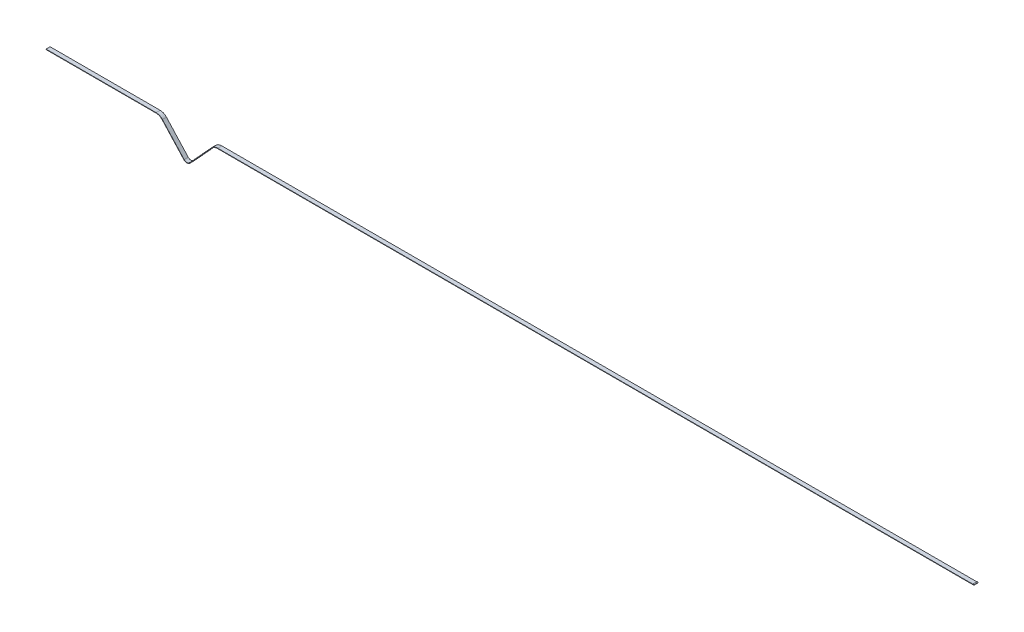
SolidWorks part; units mm, degrees
material "BUTYL"
ref_plane "Front Plane" through (0, 0, 0) normal (0, 0, 1) x (1, 0, 0)
ref_plane "Top Plane" through (0, 0, 0) normal (0, 1, 0) x (1, 0, 0)
ref_plane "Right Plane" through (0, 0, 0) normal (1, 0, 0) x (0, 0, -1)
sketch "Sketch1" plane through (0, 0, 0) normal (1, 0, 0) x (0, 0, -1)
  line L1 (0, 0) -> (6, 0)
  line L2 (0, 0) -> (0, 0.63)
  line L3 (0, 0.63) -> (6, 0.63)
  line L4 (6, 0) -> (6, 0.63)
  dimension "D1" = 0.63
  dimension "D2" = 6
sketch "Sketch2" plane through (0, 0, 0) normal (0, 0, 1) x (1, 0, 0)
  line L0 (0, 0) -> (-1117.7511, 0)
  line L1 (-1126.5701, -3.886) -> (-1158.812, -39.1468)
  line L2 (-1167.8303, -39.1468) -> (-1200.0721, -3.886)
  line L3 (-1208.8911, 0) -> (-1371.6, 0)
  arc A0 (-1117.7511, 0) -> (-1126.5701, -3.886) centre (-1117.7511, -11.95) ccw
  arc A1 (-1158.812, -39.1468) -> (-1167.8303, -39.1468) centre (-1163.3211, -35.0237) cw
  arc A2 (-1200.0721, -3.886) -> (-1208.8911, 0) centre (-1208.8911, -11.95) ccw
  circle A3 centre (-1117.7511, -11.95) radius 11.95 construction
  circle A4 centre (-1208.8911, -11.95) radius 11.95 construction
  circle A5 centre (-1163.3211, -35.0237) radius 6.11 construction
  dimension "D1" = 6.11
  dimension "D4" = 1371.6
sweep "Sweep1" add profiles "Sketch1" path "Sketch2"
sketch "Sketch3" plane through (0, 0, 0) normal (0, 0, 1) x (1, 0, 0)
  line L0 (0, 0.63) -> (-1117.7511, 0.63) construction
  line L1 (-1.5, 0.63) -> (-1.5, 0)
  line L2 (0, 0) -> (-1117.7511, 0) construction
  line L3 (-1.5, 0) -> (0, 0)
  line L4 (0, 0) -> (0, 0.63)
  arc A1 (0, 0.63) -> (-1.5, 0.63) centre (-0.75, 0.63) ccw
  dimension "D1" = 0.75
extrude "Boss-Extrude1" add sketch "Sketch3" against normal through all
pattern_curve "CrvPattern1" [suppressed] of bodies 102 driven by "Sketch2" parameters "D1"=2000, "D3"=2, "D2"=1, "D4"=10
